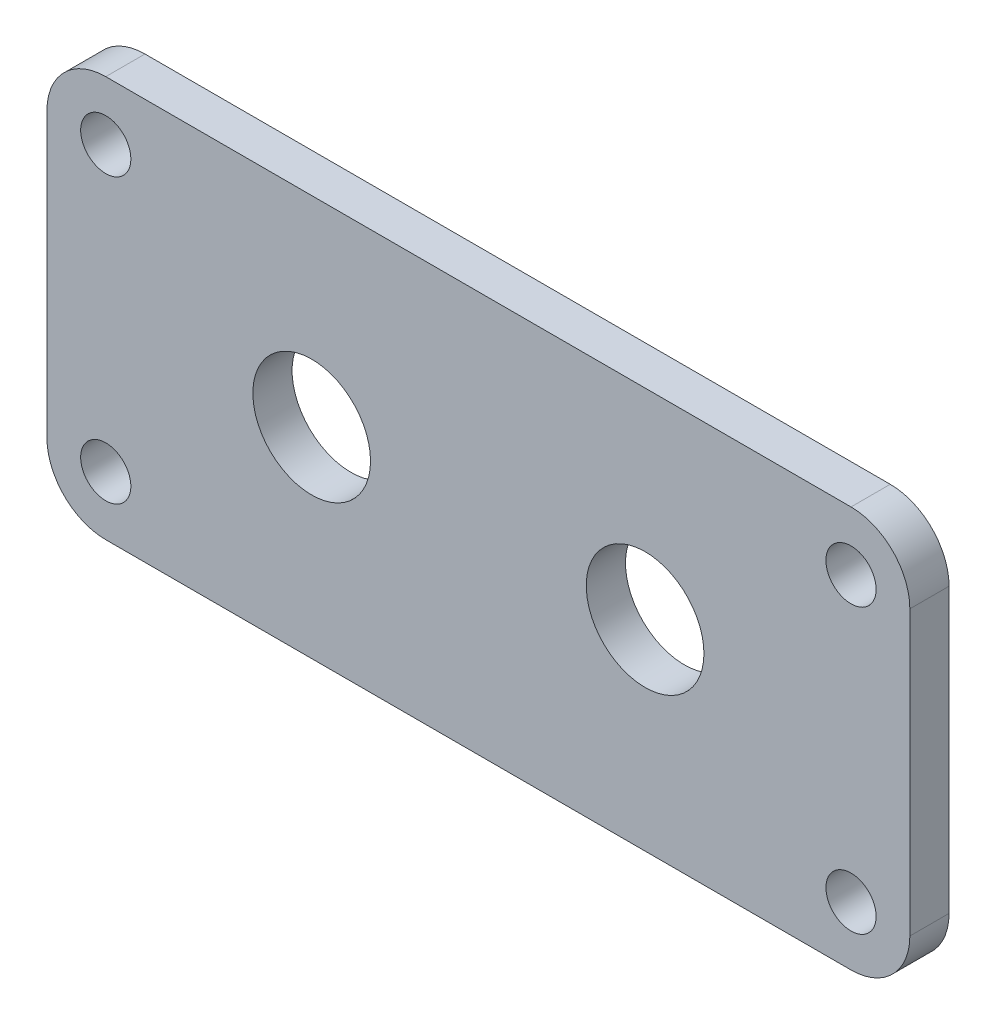
SolidWorks part; units mm, degrees
ref_plane "Front Plane" through (0, 0, 0) normal (0, 0, 1) x (1, 0, 0)
ref_plane "Top Plane" through (0, 0, 0) normal (0, 1, 0) x (1, 0, 0)
ref_plane "Right Plane" through (0, 0, 0) normal (1, 0, 0) x (0, 0, -1)
sketch "Sketch1" plane through (0, 0, 0) normal (0, 0, 1) x (1, 0, 0)
  line L0 (0, 0) -> (26.9875, 0) construction
  line L2 (43.6562, -16.2306) -> (-16.6688, -16.2306)
  line L3 (48.4187, -11.4681) -> (48.4187, 11.4681)
  line L4 (43.6562, 16.2306) -> (-16.6688, 16.2306)
  line L5 (-21.4312, -11.4681) -> (-21.4312, 11.4681)
  line L6 (48.4187, -16.2306) -> (-21.4312, 16.2306) construction
  line L7 (48.4187, 16.2306) -> (-21.4312, -16.2306) construction
  circle A0 centre (0, 0) radius 4.7625
  circle A1 centre (26.9875, 0) radius 4.7625
  arc A2 (48.4187, 11.4681) -> (43.6562, 16.2306) centre (43.6562, 11.4681) ccw
  arc A3 (43.6562, -16.2306) -> (48.4187, -11.4681) centre (43.6562, -11.4681) ccw
  arc A4 (-16.6688, -16.2306) -> (-21.4312, -11.4681) centre (-16.6688, -11.4681) cw
  arc A5 (-16.6688, 16.2306) -> (-21.4312, 11.4681) centre (-16.6688, 11.4681) ccw
  circle A6 centre (0, 0) radius 13.7592 construction
  circle A7 centre (26.9875, 0) radius 15.3467 construction
  circle A8 centre (-16.6688, 11.4681) radius 2.032
  circle A9 centre (43.6562, 11.4681) radius 2.032
  circle A10 centre (-16.6688, -11.4681) radius 2.032
  circle A11 centre (43.6562, -11.4681) radius 2.032
  point P5 (13.4937, 0)
  dimension "D1" = 9.525
  dimension "D2" = 26.9875
  dimension "D5" = 4.7625
  dimension "D6" = 27.5184
  dimension "D7" = 30.6934
  dimension "D8" = 4.064
  dimension "D3" = 32.4612
  dimension "D4" = 69.85
extrude "Boss-Extrude1" add sketch "Sketch1" along normal blind 3.175
